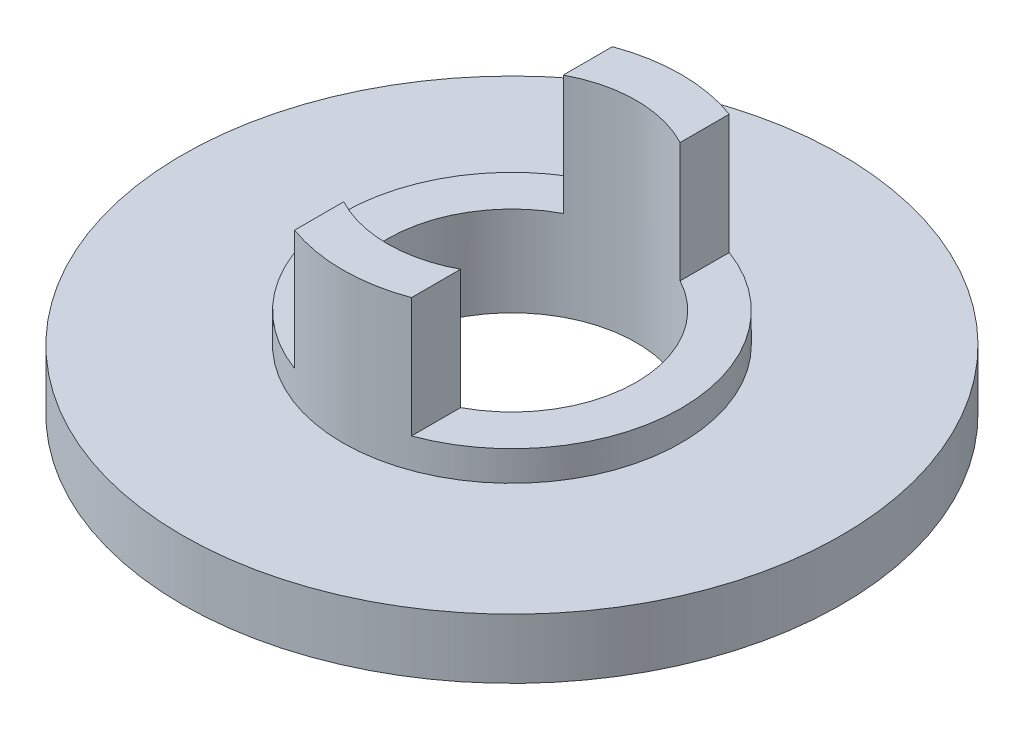
SolidWorks part; units mm, degrees
other "标注1"
sketch "草图3" plane through (-11, 9, 11) normal (-0.0956, 0.99, 0.1036) x (0.8293, 0.1368, -0.5418)
ref_plane "前视基准面" through (0, 0, 0) normal (0, 0, 1) x (1, 0, 0)
ref_plane "上视基准面" through (0, 0, 0) normal (0, 1, 0) x (1, 0, 0)
ref_plane "右视基准面" through (0, 0, 0) normal (1, 0, 0) x (0, 0, -1)
sketch "草图1" plane through (0, 0, 0) normal (0, 1, 0) x (1, 0, 0)
  circle A1 centre (0, 0) radius 5.65
  circle A2 centre (0, 0) radius 11
  circle A3 centre (0, 0) radius 4.15
  dimension "D1" = 11.3
  dimension "D2" = 22
  dimension "D3" = 1.5
extrude "凸台-拉伸1" add sketch "草图1" against normal blind 2 contours A2 | A3
extrude "凸台-拉伸2" add sketch "草图1<3>" along normal blind 5 contours A1 A3 region at (-5.4902, 0, 0)
sketch "草图1<3>" plane through (0, 0, 0) normal (0, 1, 0) x (1, 0, 0) same geometry as "草图1"
sketch "草图2" plane through (0, 5, 0) normal (0, 1, 0) x (1, 0, 0)
  line L0 (0, 0) -> (0, 50000) construction
  line L1 (1.95, 5.3028) -> (1.95, 3.6633)
  line L2 (-1.95, 5.3028) -> (-1.95, 3.6633)
  line L3 (1.95, -3.6633) -> (1.95, -5.3028)
  line L4 (-1.95, -3.6633) -> (-1.95, -5.3028)
  circle A1 centre (0, 0) radius 4.15 construction
  arc A3 (-1.95, 3.6633) -> (-1.95, -3.6633) centre (0, 0) ccw
  circle A4 centre (0, 0) radius 5.65 construction
  arc A5 (-1.95, 5.3028) -> (-1.95, -5.3028) centre (0, 0) ccw
  arc A6 (0, 5.65) -> (-1.95, 5.3028) centre (0, 0) ccw construction
  arc A7 (0, 4.15) -> (-1.95, 3.6633) centre (0, 0) ccw construction
  arc A8 (1.95, 5.3028) -> (0, 5.65) centre (0, 0) ccw construction
  arc A9 (1.95, 3.6633) -> (0, 4.15) centre (0, 0) ccw construction
  arc A10 (-1.95, -3.6633) -> (0, -4.15) centre (0, 0) ccw construction
  arc A11 (1.95, -3.6633) -> (1.95, 3.6633) centre (0, 0) ccw
  arc A12 (-1.95, -5.3028) -> (0, -5.65) centre (0, 0) ccw construction
  arc A13 (1.95, -5.3028) -> (1.95, 5.3028) centre (0, 0) ccw
  arc A14 (0, -4.15) -> (1.95, -3.6633) centre (0, 0) ccw construction
  arc A15 (0, -5.65) -> (1.95, -5.3028) centre (0, 0) ccw construction
  dimension "D1" = 1.95
extrude "切除-拉伸1" cut sketch "草图2" against normal blind 4
